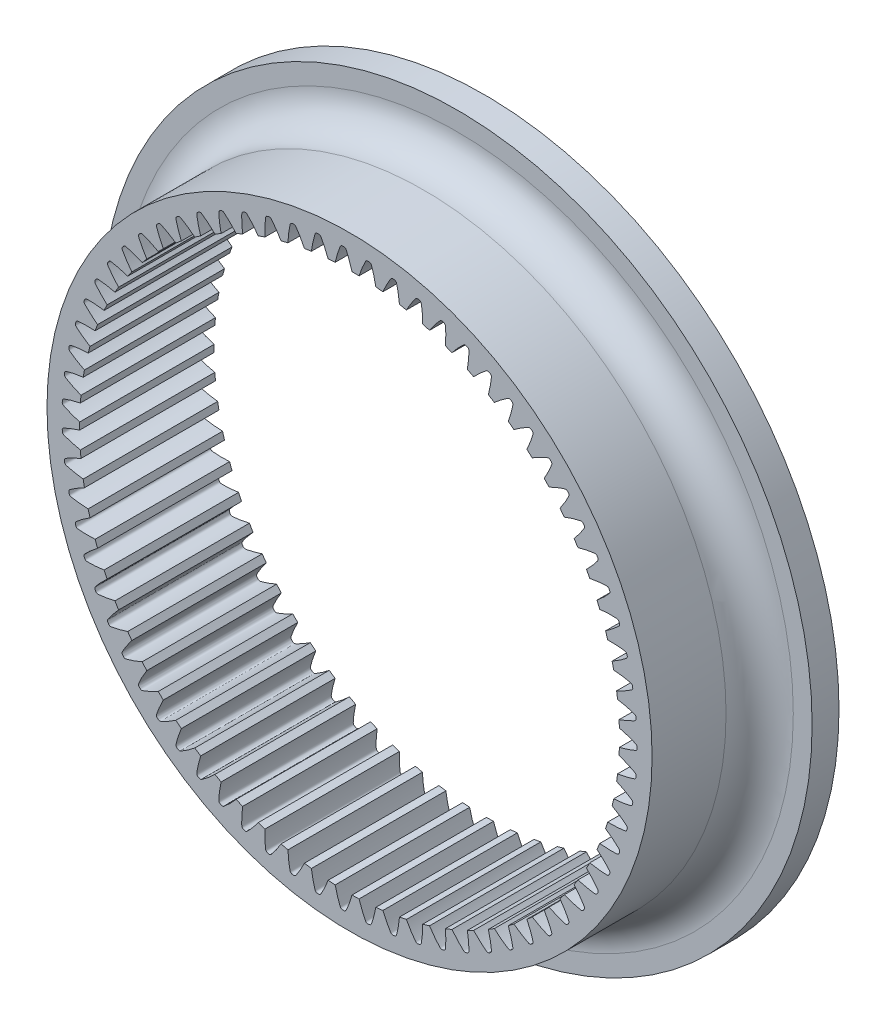
SolidWorks part; units mm, degrees
ref_plane "Front Plane" through (0, 0, 0) normal (0, 0, 1) x (1, 0, 0)
ref_plane "Top Plane" through (0, 0, 0) normal (0, 1, 0) x (1, 0, 0)
ref_plane "Right Plane" through (0, 0, 0) normal (1, 0, 0) x (0, 0, -1)
ref_axis "Axis1" through (0, 0, 6.985) along (0, 0, -1)
sketch "SketchRevolveRing_Gear_Follower02" plane through (0, 0, 0) normal (1, 0, 0) x (0, 0, -1)
  line L0 (0, 0) -> (25.4, 0) construction
  line L1 (-6.35, 25.4945) -> (-6.35, 38.1)
  line L2 (-6.35, 38.1) -> (6.35, 38.1)
  line L3 (6.35, 38.1) -> (6.35, 25.4945)
  line L4 (6.35, 25.4945) -> (-6.35, 25.4945)
  dimension "Side1" = 6.35
  dimension "OutsideRadius" = 38.1
  dimension "Side2" = 6.35
  dimension "MinorDiameter" = 25.4945
revolve "Ring_Gear_Follower02" add sketch "SketchRevolveRing_Gear_Follower02" angle 360 about L0
sketch "SketchToothRing_Gear_Follower02" plane through (0, 0, 0) normal (0, 0, 1) x (1, 0, 0)
  arc A0 (25.3229, -0.8287) -> (25.3229, 0.8287) centre (0, 0) ccw
  spline S0 degree 3 poles (25.3229, 0.8287) (25.4112, 0.8108) (25.5484, 0.7796) (25.737, 0.7307) (25.8937, 0.6865) (26.06, 0.6358) (26.2357, 0.5781) (26.4206, 0.513) (26.6146, 0.4404) (26.8165, 0.3579) (26.9656, 0.2993) (27.0537, 0.2557) (27.0798, 0.2362) (27.1027, 0.2137) (27.1221, 0.1881) (27.1375, 0.1599) (27.1526, 0.1203) (27.1579, 0.0772) (27.157, 0.0338) (27.1573, 0) (27.157, -0.0338) (27.1579, -0.0772) (27.1526, -0.1203) (27.1375, -0.1599) (27.1221, -0.1881) (27.1027, -0.2137) (27.0798, -0.2362) (27.0537, -0.2557) (26.9656, -0.2993) (26.8165, -0.3579) (26.6146, -0.4404) (26.4206, -0.513) (26.2357, -0.5781) (26.06, -0.6358) (25.8937, -0.6865) (25.737, -0.7307) (25.5484, -0.7796) (25.4112, -0.8108) (25.3229, -0.8287) knots 0 0 0 0 0.063805 0.09963 0.13807 0.179124 0.222794 0.269078 0.317977 0.369491 0.42362 0.431438 0.438996 0.446554 0.454113 0.461671 0.469229 0.484048 0.492024 0.5 0.507976 0.515952 0.530771 0.538329 0.545887 0.553446 0.561004 0.568562 0.57638 0.630509 0.682023 0.730922 0.777206 0.820876 0.86193 0.90037 0.936195 1 1 1 1
extrude "ToothExtrudeCutRing_Gear_Follower02" cut sketch "SketchToothRing_Gear_Follower02" against normal blind 6.35 and the other way blind 6.35
ref_axis "Axis2" through (29.8729, 0, 0) along (-1, 0, 0)
ref_plane "Plane1" through (0, 0, 0) normal (0, 0, -1) x (1, 0, 0)
pattern_circular "PatternRing_Gear_Follower02" count 71 every 5.07 about axis through (0, 0, 6.985) along (0, 0, -1) of "ToothExtrudeCutRing_Gear_Follower02"
sketch "AuxiliarySketchRing_Gear_Follower02" plane through (0, 0, 0) normal (0, 0, 1) x (1, 0, 0)
  circle A0 centre (0, 0) radius 26.2335 construction
  circle A1 centre (0, 0) radius 24.6514 construction
  circle A2 centre (0, 0) radius 27.1572 construction
  circle A3 centre (0, 0) radius 25.4945 construction
  dimension "PitchDiameter" = 52.467
  dimension "BaseDiameter" = 49.3028
  dimension "MajorDiameter" = 54.3144
  dimension "MinorDiameter" = 50.989
sketch "Sketch1" plane through (0, 0, 6.35) normal (0, 0, 1) x (1, 0, 0)
  circle A0 centre (0, 0) radius 28.575
  circle A1 centre (0, 0) radius 38.1
  dimension "D1" = 57.15
  dimension "D2" = 76.2
extrude "Cut-Extrude1" cut sketch "Sketch1" against normal blind 10.16
sketch "Sketch2" plane through (0, 0, -3.81) normal (0, 0, 1) x (1, 0, 0)
  circle A0 centre (0, 0) radius 33.528
  circle A1 centre (0, 0) radius 38.1
  dimension "D1" = 67.056
  dimension "D2" = 76.2
extrude "Cut-Extrude2" cut sketch "Sketch2" against normal through all
sketch "Sketch3" plane through (0, 0, 0) normal (1, 0, 0) x (0, 0, -1)
  line L0 (-6.35, 0) -> (-6.35, 28.575) construction
  line L1 (-6.35, 0.7941) -> (-6.35, -0.7941) construction
  line L2 (0.635, 28.575) -> (3.81, 28.575)
  line L3 (3.81, 33.528) -> (3.81, -33.528) construction
  line L4 (3.81, 33.528) -> (6.35, 33.528) construction
  line L5 (6.35, 33.528) -> (6.35, 0) construction
  line L6 (6.35, -33.528) -> (6.35, 33.528) construction
  line L7 (-7.2508, 31.75) -> (11.53, 31.75) construction
  line L8 (-6.985, 0) -> (6.985, 0) construction
  line L9 (0.635, 28.575) -> (0.635, 31.75) construction
  line L10 (0.635, 31.75) -> (3.81, 31.75) construction
  line L11 (3.81, 28.575) -> (3.81, 31.75)
  arc A0 (3.81, 31.75) -> (0.635, 28.575) centre (0.635, 31.75) cw
  dimension "D2" = 3.175
  dimension "D1" = 31.75
  dimension "D3" = 28.575
revolve "Revolve1" add sketch "Sketch3" angle 360 about axis through (0, 0, 6.985) along (0, 0, -1)
